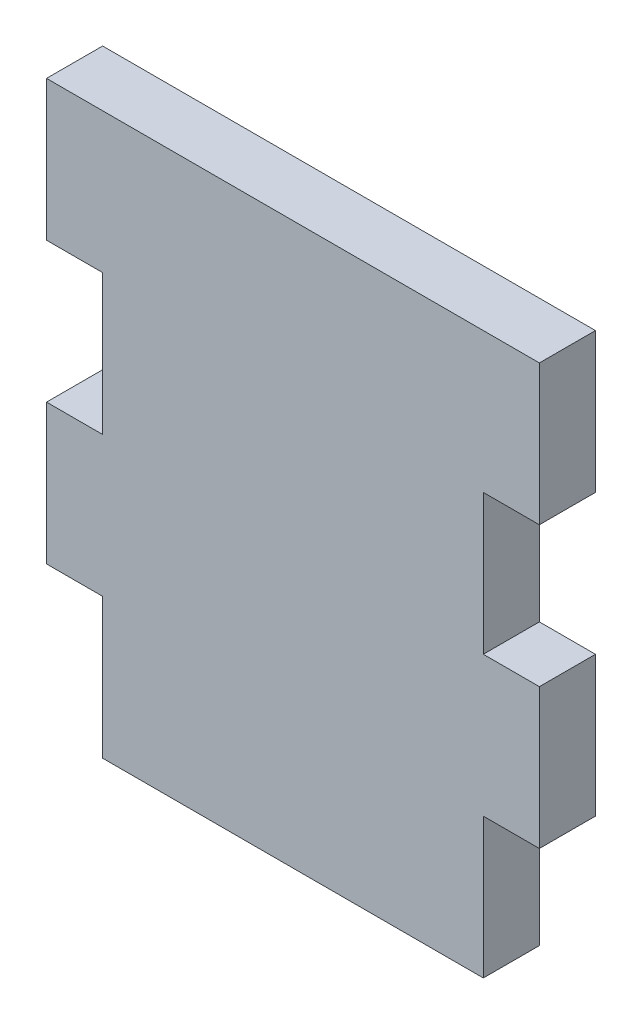
SolidWorks part; units mm, degrees
ref_plane "Front Plane" through (0, 0, 0) normal (0, 0, 1) x (1, 0, 0)
ref_plane "Top Plane" through (0, 0, 0) normal (0, 1, 0) x (1, 0, 0)
ref_plane "Right Plane" through (0, 0, 0) normal (1, 0, 0) x (0, 0, -1)
sketch "Sketch1" plane through (0, 0, 0) normal (0, 0, 1) x (1, 0, 0)
  line L1 (-88.0852, 14.1109) -> (-45.6672, 14.1109)
  line L2 (-88.0852, 14.1109) -> (-88.0852, -34.1491)
  line L3 (-88.0852, -34.1491) -> (-45.6672, -34.1491)
  line L4 (-45.6672, 14.1109) -> (-45.6672, -34.1491)
  dimension "D1" = 48.26
  dimension "D2" = 42.418
extrude "Boss-Extrude1" add sketch "Sketch1" along normal blind 4.826
sketch "Sketch2" plane through (0, 0, 4.826) normal (0, 0, 1) x (1, 0, 0)
  line L0 (-88.0852, 14.1109) -> (-88.0852, -34.1491) construction
  line L1 (-88.0852, -34.1491) -> (-83.2592, -34.1491)
  line L2 (-88.0852, -34.1491) -> (-88.0852, -22.0841)
  line L3 (-88.0852, -22.0841) -> (-83.2592, -22.0841)
  line L4 (-83.2592, -34.1491) -> (-83.2592, -22.0841)
  line L5 (-88.0852, -10.0191) -> (-83.2592, -10.0191)
  line L6 (-88.0852, -10.0191) -> (-88.0852, 2.0459)
  line L7 (-88.0852, 2.0459) -> (-83.2592, 2.0459)
  line L8 (-83.2592, -10.0191) -> (-83.2592, 2.0459)
  line L9 (-83.2592, 2.0459) -> (-83.2592, 14.1109) construction
  line L10 (-45.6672, 14.1109) -> (-88.0852, 14.1109) construction
  line L11 (-83.2592, -10.0191) -> (-83.2592, -22.0841) construction
  line L12 (-66.8762, 14.1109) -> (-66.8762, -34.1491) construction
  line L13 (-88.0852, -34.1491) -> (-45.6672, -34.1491) construction
  line L14 (-50.4932, -10.0191) -> (-50.4932, -22.0841) construction
  line L15 (-50.4932, 2.0459) -> (-50.4932, 14.1109) construction
  line L16 (-50.4932, -10.0191) -> (-50.4932, 2.0459)
  line L17 (-45.6672, 2.0459) -> (-50.4932, 2.0459)
  line L18 (-45.6672, -10.0191) -> (-45.6672, 2.0459)
  line L19 (-45.6672, -10.0191) -> (-50.4932, -10.0191)
  line L20 (-50.4932, -34.1491) -> (-50.4932, -22.0841)
  line L21 (-45.6672, -22.0841) -> (-50.4932, -22.0841)
  line L22 (-45.6672, -34.1491) -> (-45.6672, -22.0841)
  line L23 (-45.6672, -34.1491) -> (-50.4932, -34.1491)
  dimension "D1" = 4.826
extrude "Cut-Extrude1" cut sketch "Sketch2" against normal through all
equation "\"MDF\"= 0.19in"
equation "\"Foamcore\"= .13in"
equation "\"Gmaterial\"= \"MDF\""
equation "\"D1@Boss-Extrude1\"=\"MDF\""
equation "\"D1@Sketch2\"=\"MDF\""
equation "\"D2@Sketch1\"=\"MDF\"+\"MDF\"+1.29"
equation "\"PVCID\" = 2.067in"
equation "\"PVCOD\" = 2.375in"
equation "\"GenDiameter\"= 60mm"
equation "\"GenCutDiameter\" = 1.8in"
equation "\"GenCutDistance\" = 1"
equation "\"TowerHeight\" = 6in"
equation "\"TowerFrontBase\" = 3in"
equation "\"FunnelHeight\" = 1in"
equation "\"FunnelAngle\" = 20"
equation "\"TowerSideBase\" = 3in"
equation "\"TowerPanelLength\" = 2in"
equation "\"TowerPanelLeeway\" = 0.5in"
equation "\"BaseLength\" = 9in"
equation "\"BaseWidth\" = 10.5in"
equation "\"WheelHoleLength\" = 3.25in"
equation "\"WheelHoleWidth\" = 26mm"
equation "\"WheelHoleFromBack\" = 1in"
equation "\"DropLength\" = 1in"
equation "\"DropWidth\" = 8.5in"
equation "\"BumperWidth\" = 1in"
equation "\"HoleDiameter\" = 0.25in"
equation "\"SmallHexDiameter\" = 0.185in"
equation "\"SmallHexHeight\" = 0.701in"
equation "\"ScrewSize\" = 0.106in"
equation "\"BigHexDiameter\" = 0.251in"
equation "\"BigHexHeight\" = 0.374in"
equation "\"PCBThickness\" = 0.066in"
equation "\"ConnectorHeight\" = 0.517in"
equation "\"BoardHeight\" = 0.583in"
equation "\"UnoStackHeight\" = 1.351in"
equation "\"UnoStackWidth\" = 3.053in"
equation "\"UnoStackLength\" = 3.152in"
equation "\"HBridgeWidth\" = 1.797in"
equation "\"HBridgeLength\" = 2.236in"
equation "\"DSWidth\" = 1.820in"
equation "\"DSLength\" = 1.833in"
equation "\"StepperWidth\" = 1.799in"
equation "\"StepperLength\" = 2.248in"
equation "\"ULNWidth\" = 1.304in"
equation "\"ULNLength\" = 1.545in"
equation "\"VSwitchHeight\" = 0.392in"
equation "\"VSwitchWidth\" = 0.637in"
equation "\"VSwitchLength\" = 1.097in"
equation "\"SkateWheelDiameter\" = 80mm"
equation "\"SkateWheelThickness\" = 24mm"
equation "\"BaseDistance\" = 3in"
